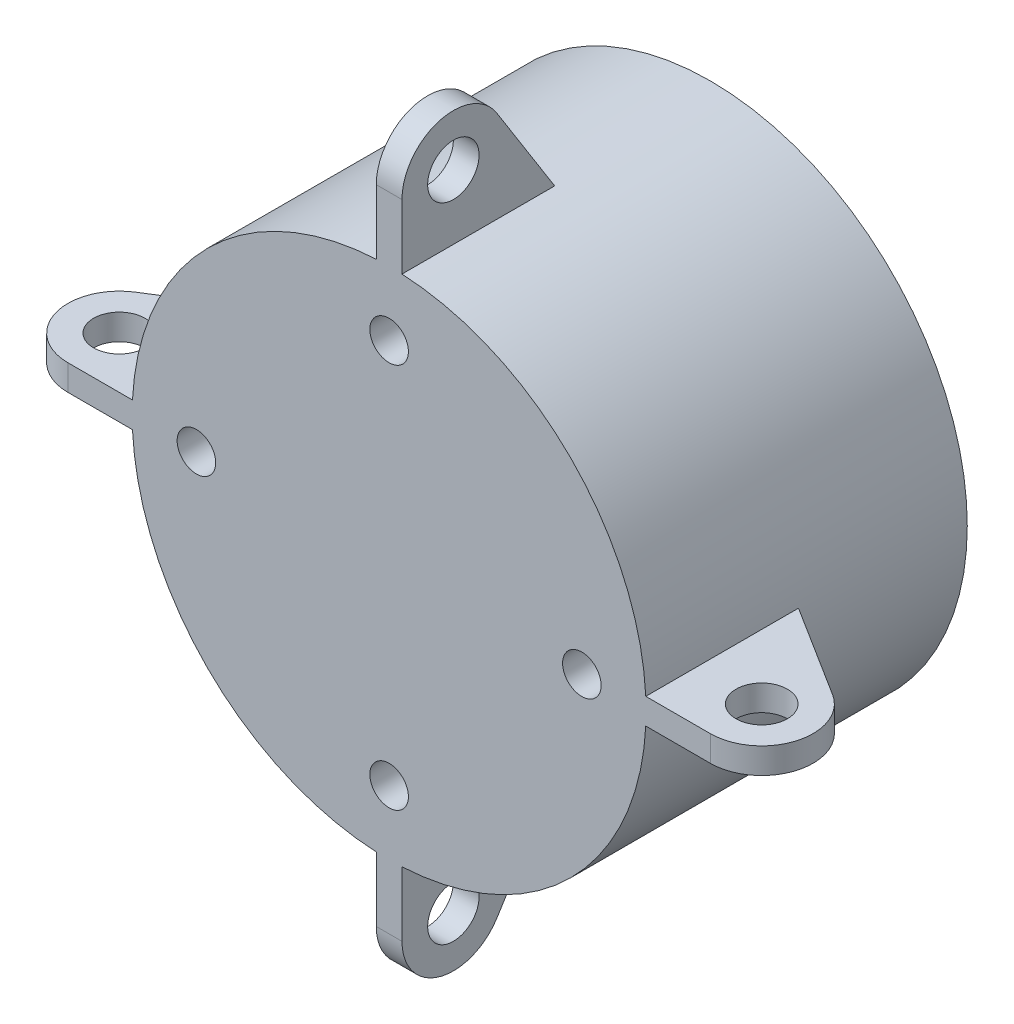
SolidWorks part; units mm, degrees
material "ABS"
ref_plane "前视基准面" through (0, 0, 0) normal (0, 0, 1) x (1, 0, 0)
ref_plane "上视基准面" through (0, 0, 0) normal (0, 1, 0) x (1, 0, 0)
ref_plane "右视基准面" through (0, 0, 0) normal (1, 0, 0) x (0, 0, -1)
sketch "草图1" plane through (0, 0, 0) normal (0, 0, 1) x (1, 0, 0)
  circle A0 centre (0, 0) radius 40
  dimension "D1" = 80
extrude "凸台-拉伸1" add sketch "草图1" against normal blind 50
sketch "草图2" plane through (0, 0, 0) normal (0, 0, 1) x (1, 0, 0)
  line L0 (0, 30) -> (0, 0) construction
  line L1 (0, 0) -> (0, -30) construction
  line L2 (-30, 0) -> (0, 0) construction
  line L3 (0, 0) -> (30, 0) construction
  circle A0 centre (0, 30) radius 3
  circle A1 centre (30, 0) radius 3
  circle A2 centre (0, -30) radius 3
  circle A3 centre (-30, 0) radius 3
  dimension "D1" = 6
  dimension "D2" = 6
  dimension "D3" = 6
  dimension "D4" = 6
  dimension "D5" = 30
  dimension "D6" = 30
  dimension "D7" = 30
  dimension "D8" = 30
extrude "切除-拉伸1" cut sketch "草图2" against normal blind 10
sketch "草图3" plane through (0, 0, 0) normal (1, 0, 0) x (0, 0, -1)
  line L0 (25, 38) -> (0, 38)
  line L1 (0, 38) -> (0, 50)
  line L2 (14.7716, 54.2598) -> (25, 38)
  line L3 (0, 40) -> (0, -40) construction
  arc A0 (0, 50) -> (14.7716, 54.2598) centre (8, 50) cw
  circle A1 centre (8, 50) radius 4
  dimension "D2" = 8
  dimension "D6" = 8
  dimension "D1" = 25
  dimension "D3" = 0
  dimension "D4" = 38
  dimension "D5" = 12
extrude "凸台-拉伸2" add sketch "草图3" along normal blind 2 and the other way blind 2
pattern_circular "阵列(圆周)1" count 4 every 90 about axis through (0, 0, -50) along (0, 0, 1) of "凸台-拉伸2"
